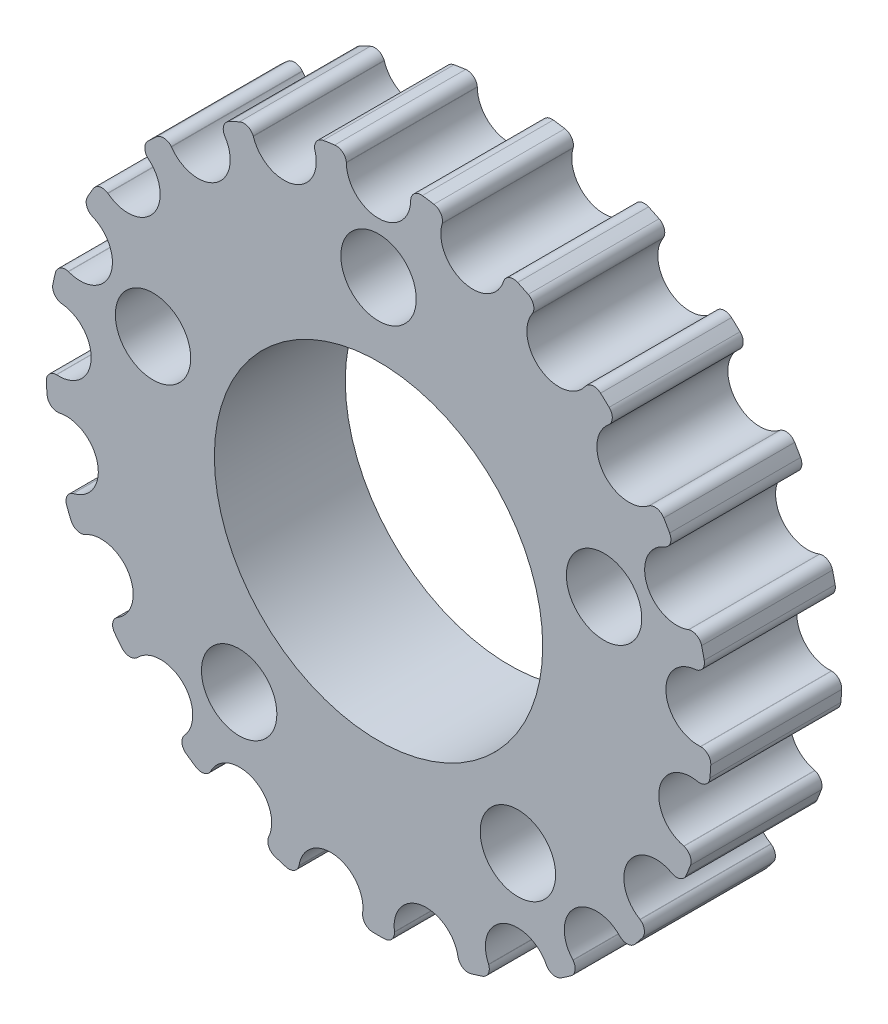
SolidWorks part; units mm, degrees
material "6061-T6 (SS)"
ref_plane "Front Plane" through (0, 0, 0) normal (0, 0, 1) x (1, 0, 0)
ref_plane "Top Plane" through (0, 0, 0) normal (0, 1, 0) x (1, 0, 0)
ref_plane "Right Plane" through (0, 0, 0) normal (1, 0, 0) x (0, 0, -1)
sketch "Pitch diameter" plane through (0, 0, 0) normal (0, 0, 1) x (1, 0, 0)
  circle A0 centre (0, 0) radius 16.7113 construction
  dimension "D1" = 33.4225
sketch "Sketch2" plane through (0, 0, 0) normal (0, 0, 1) x (1, 0, 0)
  circle A0 centre (0, 0) radius 16.1398
  dimension "D1" = 32.2795
extrude "Boss-Extrude1" add sketch "Sketch2" along normal blind 6.35
sketch "Sketch3" plane through (0, 0, 0) normal (0, 0, -1) x (-1, 0, 0)
  line L0 (-1.6121, 16.0591) -> (-1.56, 15.5398)
  line L1 (1.6121, 16.0591) -> (1.56, 15.5398)
  line L2 (-1.56, 15.5398) -> (1.56, 15.5398) construction
  circle A0 centre (0, 0) radius 16.1398 construction
  arc A1 (-1.56, 15.5398) -> (1.56, 15.5398) centre (0, 15.5398) ccw
  circle A2 centre (0, 0) radius 16.1398 construction
  arc A3 (1.6121, 16.0591) -> (-1.6121, 16.0591) centre (0, 0) ccw
  point P10 (0, 15.5398)
  point P15 (0, 13.9798)
  point P16 (0, 16.1398)
  dimension "D1" = 1.56
  dimension "D2" = 2.16
extrude "Cut-Extrude1" cut sketch "Sketch3" against normal through all
fillet "Fillet1" radius 0.5 2 edges at (-1.6121, 16.0591, 3.175) (1.6121, 16.0591, 3.175)
pattern_circular "CirPattern1" count 21 over 360 about axis through (0, 0, 0) along (0, 0, 1) of "Cut-Extrude1", "Fillet1"
sketch "Sketch4" plane through (0, 0, 6.35) normal (0, 0, 1) x (1, 0, 0)
  circle A0 centre (0, 0) radius 7.9629
  dimension "D1" = 15.9258
extrude "Cut-Extrude2" cut sketch "Sketch4" against normal through all
sketch "Sketch5" plane through (0, 0, 6.35) normal (0, 0, 1) x (1, 0, 0)
  line L0 (0, 0) -> (0, 11.5)
  point P0 (0, 0)
  point P7 (0, 0)
  dimension "D1" = 11.5
sketch "Sketch9" plane through (0, 0, 6.35) normal (0, 0, 1) x (1, 0, 0)
  point P0 (0, 11.5)
hole_wizard "#6 Clearance Hole1" positions "Sketch9" profile "Sketch10" hole size "#6" standard "ANSI Inch" end condition through all
sketch "Sketch10" plane through (0, 11.5, 6.35) normal (1, 0, 0) x (0, -1, 0)
  line L0 (0, 0) -> (0, 6.35)
  line L1 (0, 6.35) -> (1.8288, 6.35)
  line L2 (1.8288, 6.35) -> (1.8288, 0)
  line L5 (1.8288, 0) -> (0, 0)
  line L11 (0, -6.35) -> (0, 107.95) construction
  dimension "Thru Hole Dia." = 3.6576
  dimension "Thru Hole Depth" = 6.35
pattern_circular "CirPattern2" count 5 over 360 about axis through (0, 0, 6.35) along (0, 0, 1) of "#6 Clearance Hole1"
equation "\"NumberOfTeeth\"= 21"
equation "\"Pitch\"= 5mm"
equation "\"PitchDiameter\"= ( \"Pitch\" * \"NumberOfTeeth\" ) / Pi"
equation "\"OD\"= \"PitchDiameter\" - 0.0225in * 2"
equation "\"D1@Pitch diameter\" = \"PitchDiameter\""
equation "\"D1@Sketch2\"=\"OD\""
equation "\"D1@CirPattern1\"=\"NumberOfTeeth\""
